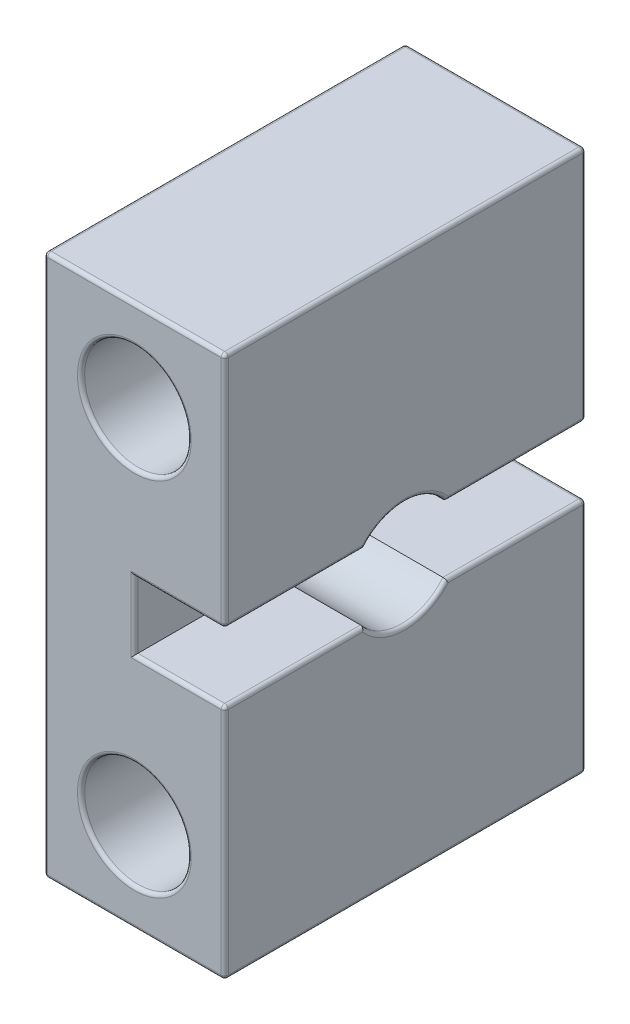
SolidWorks part; units mm, degrees
ref_plane "Front Plane" through (0, 0, 0) normal (0, 0, 1) x (1, 0, 0)
ref_plane "Top Plane" through (0, 0, 0) normal (0, 1, 0) x (1, 0, 0)
ref_plane "Right Plane" through (0, 0, 0) normal (1, 0, 0) x (0, 0, -1)
sketch "Sketch1" plane through (0, 0, 0) normal (0, 0, 1) x (1, 0, 0)
  line L1 (0, 0) -> (25.4, 0)
  line L2 (0, 0) -> (0, 76.2)
  line L3 (0, 76.2) -> (25.4, 76.2)
  line L4 (25.4, 0) -> (25.4, 76.2)
  dimension "D1" = 76.2
  dimension "D2" = 25.4
extrude "Extrude1" add sketch "Sketch1" along normal blind 50.8
hole_wizard "Ø15.0 (15) Diameter Hole1" positions "3DSketch1" profile "Sketch2" hole size "Ø15.0" standard "Ansi Metric" end condition up to next
sketch3d "3DSketch1"
  line L0 (25.4, 76.2, 50.8) -> (0, 76.2, 50.8) construction
  line L1 (0, 76.2, 50.8) -> (0, 0, 50.8) construction
  line L2 (0, 0, 50.8) -> (25.4, 0, 50.8) construction
  point P0 (12.7, 63.5, 50.8)
  point P2 (12.7, 12.7, 50.8)
  dimension "D1" = 12.7
  dimension "D2" = 12.7
  dimension "D3" = 12.7
  dimension "D4" = 12.7
sketch "Sketch2" plane through (12.7, 63.5, 50.8) normal (1, 0, 0) x (0, -1, 0)
  line L0 (0, 0) -> (0, 50.8)
  line L1 (0, 50.8) -> (7.5, 50.8)
  line L2 (7.5, 50.8) -> (7.5, 0)
  line L5 (7.5, 0) -> (0, 0)
  line L11 (0, -6.35) -> (0, 107.95) construction
  dimension "Thru Hole Dia." = 15
  dimension "Thru Hole Depth" = 50.8
hole_wizard "Ø15.0 (15) Diameter Hole3" positions "3DSketch3" profile "Sketch4" hole size "Ø15.0" standard "Ansi Metric" end condition up to next
sketch3d "3DSketch3"
  line L0 (25.4, 0, 50.8) -> (25.4, 76.2, 50.8) construction
  line L1 (25.4, 76.2, 50.8) -> (25.4, 76.2, 0) construction
  point P0 (25.4, 38.1, 25.4)
  dimension "D1" = 25.4
  dimension "D2" = 38.1
sketch "Sketch4" plane through (25.4, 38.1, 25.4) normal (0, 1, 0) x (0, 0, -1)
  line L0 (0, 0) -> (0, 25.4)
  line L1 (0, 25.4) -> (7.5, 25.4)
  line L2 (7.5, 25.4) -> (7.5, 0)
  line L5 (7.5, 0) -> (0, 0)
  line L11 (0, -6.35) -> (0, 107.95) construction
  dimension "Thru Hole Dia." = 15
  dimension "Thru Hole Depth" = 25.4
sketch "Sketch7" plane through (25.4, 0, 0) normal (1, 0, 0) x (0, 0, -1)
  line L0 (-50.8, 38.1) -> (0, 38.1) construction
  line L1 (-50.8, 0) -> (-50.8, 76.2) construction
  line L2 (0, 0) -> (0, 76.2) construction
  line L3 (-50.8, 33.3375) -> (0, 33.3375)
  line L4 (-50.8, 42.8625) -> (0, 42.8625)
  line L5 (0, 33.3375) -> (0, 42.8625)
  line L6 (-50.8, 33.3375) -> (-50.8, 42.8625)
  dimension "D1" = 4.7625
  dimension "D2" = 4.7625
extrude "Extrude2" cut sketch "Sketch7" against normal blind 12.7
fillet "Fillet1" radius 0.508 31 edges at (5.2, 12.7, 0) (5.2, 63.5, 0) (12.7, 0, 0) (19.05, 33.3375, 0) (12.7, 38.1, 0) (19.05, 42.8625, 0) (0, 0, 25.4) (0, 38.1, 0) (0, 38.1, 17.9) (0, 76.2, 25.4) (12.7, 76.2, 0) (25.4, 0, 25.4) (25.4, 33.3375, 40.9969) (25.4, 30.6, 25.4) (25.4, 33.3375, 9.8031) (25.4, 16.6687, 0) (25.4, 76.2, 25.4) (25.4, 59.5312, 0) (25.4, 42.8625, 9.8031) (25.4, 45.6, 25.4) (25.4, 42.8625, 40.9969) (19.05, 33.3375, 50.8) (25.4, 16.6687, 50.8) (12.7, 0, 50.8) (0, 38.1, 50.8) (12.7, 76.2, 50.8) (25.4, 59.5312, 50.8) (19.05, 42.8625, 50.8) (12.7, 38.1, 50.8) (20.2, 12.7, 50.8) (20.2, 63.5, 50.8)
